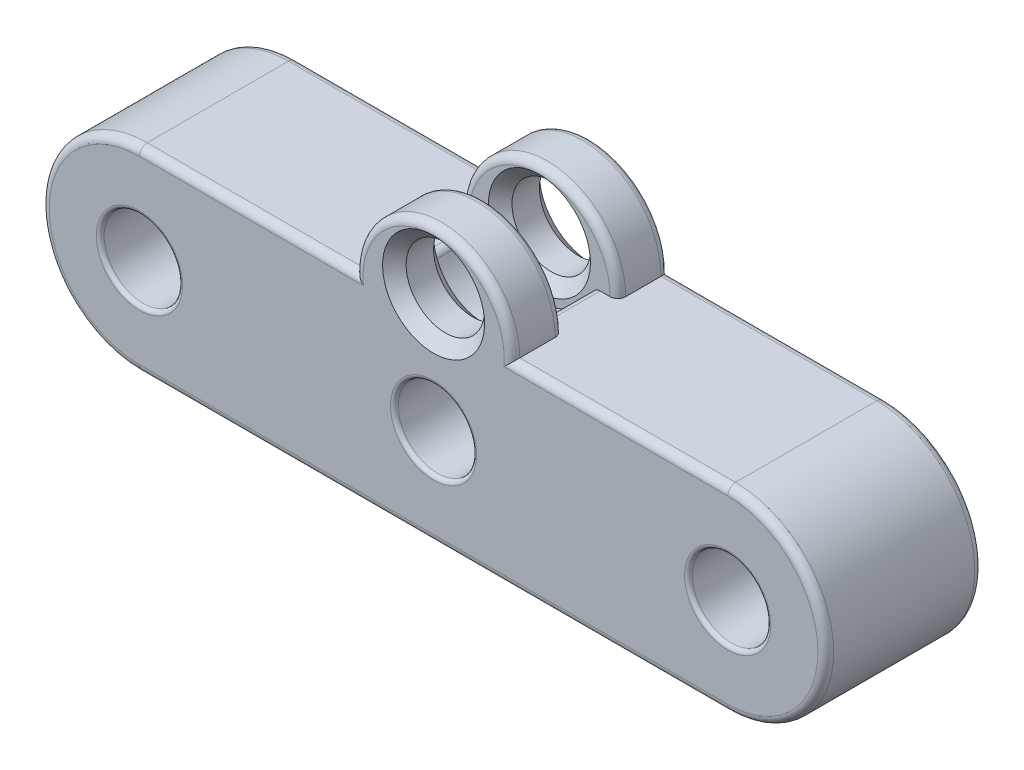
SolidWorks part; units mm, degrees
ref_plane "Plan de face" through (0, 0, 0) normal (0, 0, 1) x (1, 0, 0)
ref_plane "Plan de dessus" through (0, 0, 0) normal (0, 1, 0) x (1, 0, 0)
ref_plane "Plan de droite" through (0, 0, 0) normal (1, 0, 0) x (0, 0, -1)
sketch "Esquisse1" plane through (0, 0, 0) normal (0, 0, 1) x (1, 0, 0)
  line L0 (57.0449, 25.192) -> (57.0449, -24.808)
  line L1 (-42.9551, 25.192) -> (157.0449, 25.192)
  line L2 (-42.9551, 25.192) -> (-42.9551, -24.808)
  line L3 (-42.9551, -24.808) -> (157.0449, -24.808)
  line L4 (157.0449, 25.192) -> (157.0449, -24.808)
  circle A0 centre (57.0449, 0.192) radius 10
  circle A1 centre (-17.9551, 0.192) radius 25
  circle A2 centre (132.0449, 0.192) radius 25
  circle A3 centre (-17.9551, 0.192) radius 10
  circle A4 centre (132.0449, 0.192) radius 10
  dimension "D1" = 50
  dimension "D2" = 200
extrude "Boss.-Extru.1" add sketch "Esquisse1" along normal blind 40 contours A1 A3 | A1 L3 L0 A0 L1 | A2 L1 L0 A0 L3 | A2 A4 region at (86.4354, 0.192, 0) region at (27.6543, 0.192, 0) region at (-0.7775, 17.3697, 0) region at (149.2225, 17.3697, 0)
sketch "Esquisse2" plane through (0, 0, 0) normal (0, 0, -1) x (-1, 0, 0)
  line L0 (-57.0449, 10.192) -> (-57.0449, 25.192)
  line L1 (17.9551, 25.192) -> (-132.0449, 25.192) construction
  line L3 (-57.0449, 35.192) -> (-57.0449, 25.192)
  line L4 (-57.0449, 35.192) -> (-57.0449, 25.192)
  circle A0 centre (-57.0449, 0.192) radius 10 construction
  circle A1 centre (-57.0449, 25.192) radius 20
  circle A2 centre (-57.0449, 30.192) radius 10
  line M3 (17.9551, 25.192) -> (-132.0449, 25.192)
  dimension "D1" = 40
extrude "Boss.-Extru.6" add sketch "Esquisse2" against normal blind 13 contours A2 A1 M3 region at (71.375, 25.6392, 0)
ref_plane "Plan2" through (-17.9551, 25.192, 40) normal (1, 0, 0) x (0, 0, -1)
sketch "Esquisse12" plane through (0, 0, 40) normal (0, 0, 1) x (1, 0, 0)
  line L0 (-17.9551, 25.192) -> (132.0449, 25.192) construction
  line L1 (57.0449, 45.192) -> (57.0449, 25.192)
  line L2 (57.0449, 25.192) -> (57.0449, 35.192)
  line L3 (77.0449, 25.192) -> (65.7051, 25.192)
  line L4 (37.0449, 25.192) -> (48.3846, 25.192)
  circle A0 centre (57.0449, 25.192) radius 20
  circle A1 centre (57.0449, 30.192) radius 10
  point P0 (57.0449, 25.192)
  line M3 (132.0449, 25.192) -> (-17.9551, 25.192)
extrude "Boss.-Extru.7" add sketch "Esquisse12" against normal blind 13 contours A1 L1 A0 M3 | A1 A0 L1 M3 region at (45.8399, 34.8747, 40) region at (68.2498, 34.8747, 40)
sketch "Esquisse14" plane through (0, 0, 40) normal (0, 0, 1) x (1, 0, 0)
  line L0 (57.0449, 40.192) -> (57.0449, 25.192)
  line L1 (48.3846, 25.192) -> (65.7051, 25.192) construction
  line L2 (47.0449, 30.192) -> (67.0449, 30.192)
  arc A0 (65.7051, 25.192) -> (48.3846, 25.192) centre (57.0449, 30.192) ccw construction
  circle A1 centre (57.0449, 30.192) radius 10
  line M7 (65.7051, 25.192) -> (48.3846, 25.192)
extrude "Enlèv. mat.-Extru.3" cut sketch "Esquisse14" against normal blind 40 contours A1 M7 region at (57.0449, 23.1418, 40)
sketch "Esquisse16" plane through (0, 0, 27) normal (0, 0, -1) x (-1, 0, 0)
  line L0 (-57.0449, 40.192) -> (-57.0449, 30.192)
  arc A0 (-48.3846, 25.192) -> (-65.7051, 25.192) centre (-57.0449, 30.192) ccw construction
  circle A1 centre (-57.0449, 30.192) radius 15
  arc M1 (-65.7051, 25.192) -> (-48.3846, 25.192) centre (-57.0449, 30.192) cw
  line M2 (-48.3846, 25.192) -> (-37.0449, 25.192)
  line M4 (-77.0449, 25.192) -> (-65.7051, 25.192)
extrude "Enlèv. mat.-Extru.8" cut sketch "Esquisse16" along normal blind 14 contours A1 M4 M1 M2 | A1 M4 M2 M1 region at (42.6162, 27.7165, 27) region at (57.0449, 27.0273, 27)
fillet "Congé4" radius 2 16 edges at (57.0449, 45.192, 0) (57.0449, 45.192, 13) (57.0449, 45.192, 40) (57.0449, 45.192, 27) (71.187, 25.192, 20) (42.9027, 25.192, 20) (157.0449, 0.192, 40) (157.0449, 0.192, 0) (104.5449, 25.192, 0) (104.5449, 25.192, 40) (57.0449, -24.808, 40) (57.0449, -24.808, 0) (-42.9551, 0.192, 0) (-42.9551, 0.192, 40) (9.5449, 25.192, 0) (9.5449, 25.192, 40)
fillet "Congé7" radius 1 6 edges at (-7.9551, 0.192, 40) (67.0449, 0.192, 40) (142.0449, 0.192, 40) (-7.9551, 0.192, 0) (67.0449, 0.192, 0) (142.0449, 0.192, 0)
chamfer "Chanfrein2" distance 3 angle 45 4 edges at (47.0449, 30.192, 0) (67.0449, 30.192, 27) (47.0449, 30.192, 13) (67.0449, 30.192, 40)
